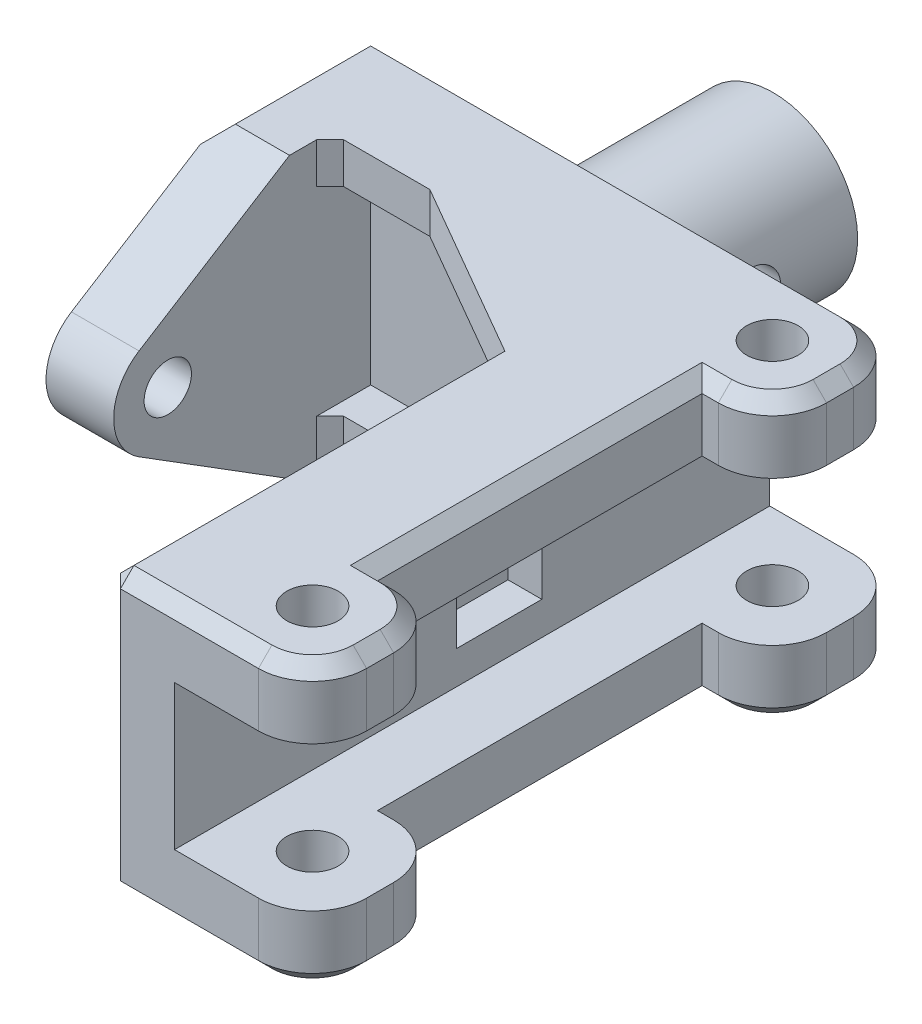
SolidWorks part; units mm, degrees
ref_plane "正面(Front)" through (0, 0, 0) normal (0, 0, 1) x (1, 0, 0)
ref_plane "平面(Top)" through (0, 0, 0) normal (0, 1, 0) x (1, 0, 0)
ref_plane "右側面(Right)" through (0, 0, 0) normal (1, 0, 0) x (0, 0, -1)
sketch "ｽｹｯﾁ1" plane through (0, 0, 0) normal (0, 0, 1) x (1, 0, 0)
  circle A0 centre (0, 0) radius 6.25
  dimension "D1" = 12.5
extrude "ﾎﾞｽ - 押し出し1" add sketch "ｽｹｯﾁ1" against normal blind 15
sketch "ｽｹｯﾁ2" plane through (0, 0, 0) normal (0, 0, 1) x (1, 0, 0)
  line L1 (-14.75, 10.35) -> (14.75, 10.35)
  line L2 (-14.75, 10.35) -> (-14.75, -10.35)
  line L3 (-14.75, -10.35) -> (14.75, -10.35)
  line L4 (14.75, 10.35) -> (14.75, -10.35)
  line L5 (-14.75, 10.35) -> (14.75, -10.35) construction
  line L6 (-14.75, -10.35) -> (14.75, 10.35) construction
  point P0 (0, 0)
  dimension "D1" = 20.7
  dimension "D2" = 29.5
extrude "ﾎﾞｽ - 押し出し2" add sketch "ｽｹｯﾁ2" along normal blind 5
sketch "ｽｹｯﾁ3" plane through (14.75, 0, 0) normal (1, 0, 0) x (0, 0, -1)
  line L0 (0, 0) -> (-31.0876, 0) construction
  line L1 (-5, 10.35) -> (-44, 10.35)
  line L3 (-44, 10.35) -> (-44, -10.35)
  line L6 (-5, -10.35) -> (-44, -10.35)
  line L7 (-5, 10.35) -> (-5, -10.35)
  circle A0 centre (-20, 0) radius 1.75
  dimension "D2" = 15
  dimension "D4" = 3.5
  dimension "D1" = 39
extrude "ﾎﾞｽ - 押し出し3" add sketch "ｽｹｯﾁ3" against normal blind 5
sketch "ｽｹｯﾁ4" plane through (14.75, 0, 0) normal (1, 0, 0) x (0, 0, -1)
  line L1 (0, 10.35) -> (-10, 10.35)
  line L2 (0, 10.35) -> (0, 5.35)
  line L3 (0, 5.35) -> (-10, 5.35)
  line L4 (-10, 10.35) -> (-10, 5.35)
  line L5 (0, -10.35) -> (-10, -10.35)
  line L6 (0, -10.35) -> (0, -5.35)
  line L7 (0, -5.35) -> (-10, -5.35)
  line L8 (-10, -10.35) -> (-10, -5.35)
  line L9 (-44, 10.35) -> (-34, 10.35)
  line L10 (-44, 10.35) -> (-44, 5.35)
  line L11 (-44, 5.35) -> (-34, 5.35)
  line L12 (-34, 10.35) -> (-34, 5.35)
  line L13 (-44, -10.35) -> (-34, -10.35)
  line L14 (-44, -10.35) -> (-44, -5.35)
  line L15 (-44, -5.35) -> (-34, -5.35)
  line L16 (-34, -10.35) -> (-34, -5.35)
  dimension "D1" = 5
  dimension "D2" = 5
  dimension "D3" = 10
  dimension "D4" = 10
extrude "ﾎﾞｽ - 押し出し4" add sketch "ｽｹｯﾁ4" along normal blind 10.2
sketch "ｽｹｯﾁ5" plane through (0, -10.35, 0) normal (0, -1, 0) x (1, 0, 0)
  line L4 (24.95, 5) -> (5.2641, 5) construction
  line L5 (24.95, 10) -> (24.95, 0) construction
  line L6 (24.95, 39) -> (4.1235, 39) construction
  line L7 (24.95, 44) -> (24.95, 34) construction
  circle A0 centre (19.95, 5) radius 1.9
  circle A2 centre (19.95, 39) radius 1.9
  dimension "D1" = 3.8
  dimension "D2" = 5
extrude "ｶｯﾄ - 押し出し1" cut sketch "ｽｹｯﾁ5" against normal through all
fillet "ﾌｨﾚｯﾄ1" radius 4 8 edges at (24.95, 7.85, 10) (24.95, 7.85, 0) (24.95, -7.85, 0) (24.95, -7.85, 10) (24.95, -7.85, 34) (24.95, 7.85, 34) (24.95, 7.85, 44) (24.95, -7.85, 44)
sketch "ｽｹｯﾁ8" plane through (14.75, 0, 0) normal (1, 0, 0) x (0, 0, -1)
  line L1 (-34, 10.35) -> (-10, 10.35)
  line L2 (-34, 10.35) -> (-34, 5.35)
  line L3 (-34, 5.35) -> (-10, 5.35)
  line L4 (-10, 10.35) -> (-10, 5.35)
  line L5 (-34, -5.35) -> (-10, -5.35)
  line L6 (-34, -5.35) -> (-34, -10.35)
  line L7 (-34, -10.35) -> (-10, -10.35)
  line L8 (-10, -5.35) -> (-10, -10.35)
extrude "ﾎﾞｽ - 押し出し6" add sketch "ｽｹｯﾁ8" along normal blind 5
sketch "ｽｹｯﾁ9" plane through (-14.75, 0, 0) normal (-1, 0, 0) x (0, 0, 1)
  line L0 (0, 0) -> (29.5336, 0) construction
  line L1 (5, 10.35) -> (11, 10.35)
  line L2 (5, 10.35) -> (44, 10.35) construction
  line L3 (11, 10.35) -> (22.1218, 3.3909)
  line L4 (11, -10.35) -> (22.1218, -3.3909)
  line L5 (5, -10.35) -> (11, -10.35)
  line L6 (5, -10.35) -> (5, 10.35)
  arc A0 (22.1218, 3.3909) -> (22.1218, -3.3909) centre (20, 0) cw
  circle A2 centre (20, 0) radius 1.75 construction
  circle A3 centre (20, 0) radius 1.75
  dimension "D1" = 4
  dimension "D3" = 3.5
  dimension "D2" = 6
extrude "ﾎﾞｽ - 押し出し7" add sketch "ｽｹｯﾁ9" against normal blind 5
sketch "ｽｹｯﾁ6" plane through (0, -10.35, 0) normal (0, -1, 0) x (1, 0, 0)
  line L3 (-9.75, 5) -> (9.75, 5) construction
  line L8 (9.75, 44) -> (9.75, 5) construction
  line L9 (-9.75, 5) -> (9.75, 5)
  line L10 (9.75, 5) -> (9.75, 15)
  line L11 (-9.75, 5) -> (9.75, 5) construction
  line L12 (-9.75, 5) -> (-9.75, 8)
  line L13 (-9.75, 5) -> (-9.75, 11) construction
  line L15 (-9.75, 8) -> (-2.3744, 8)
  line L16 (-2.3744, 8) -> (9.75, 15)
  dimension "D1" = 30
  dimension "D2" = 10
extrude "ﾎﾞｽ - 押し出し5" add sketch "ｽｹｯﾁ6" against normal blind 3
mirror "ﾐﾗｰ1" about plane through (0, 0, 0) normal (0, 1, 0) of "ﾎﾞｽ - 押し出し5"
chamfer "面取り1" distance 1 angle 45 28 edges at (19.75, 10.35, 22) (20.35, 10.35, 10) (23.7784, 10.35, 8.8284) (24.95, 10.35, 5) (23.7784, 10.35, 1.1716) (3.1, 10.35, 0) (-14.75, 10.35, 5.5) (-14.75, 0, 0) (-14.75, -10.35, 5.5) (20.35, -10.35, 10) (3.1, -10.35, 0) (23.7784, -10.35, 8.8284) (23.7784, -10.35, 1.1716) (24.95, -10.35, 5) (19.75, -10.35, 22) (20.35, 10.35, 34) (20.35, -10.35, 34) (23.7784, 10.35, 35.1716) (23.7784, -10.35, 35.1716) (24.95, 10.35, 39) (24.95, -10.35, 39) (23.7784, 10.35, 42.8284) (23.7784, -10.35, 42.8284) (15.35, 10.35, 44) (15.35, -10.35, 44) (9.75, 10.35, 29.5) (9.75, 0, 44) (9.75, -10.35, 29.5)
chamfer "面取り2" distance 1 angle 45 2 edges at (-9.75, 8.85, 8) (-9.75, -8.85, 8)
sketch "ｽｹｯﾁ10" plane through (14.75, 0, 0) normal (1, 0, 0) x (0, 0, -1)
  line L1 (-23.15, 2.9) -> (-16.85, 2.9)
  line L2 (-23.15, 2.9) -> (-23.15, -2.9)
  line L3 (-23.15, -2.9) -> (-16.85, -2.9)
  line L4 (-16.85, 2.9) -> (-16.85, -2.9)
  line L5 (-23.15, 2.9) -> (-16.85, -2.9) construction
  line L6 (-23.15, -2.9) -> (-16.85, 2.9) construction
  point P0 (-20, 0)
  dimension "D1" = 5.8
  dimension "D2" = 6.3
extrude "ｶｯﾄ - 押し出し2" cut sketch "ｽｹｯﾁ10" against normal blind 2.5
sketch "ｽｹｯﾁ11" plane through (0, 0, 0) normal (1, 0, 0) x (0, 0, -1)
  line L0 (0, 0) -> (15, 0) construction
  line L1 (15, -6.25) -> (15, 6.25) construction
  line L2 (0, -6.25) -> (0, 6.25) construction
  circle A0 centre (7.5, 0) radius 1.8
  dimension "D1" = 3.6
  dimension "D2" = 7.5
extrude "ｶｯﾄ - 押し出し3" cut sketch "ｽｹｯﾁ11" against normal through all both and the other way through all
